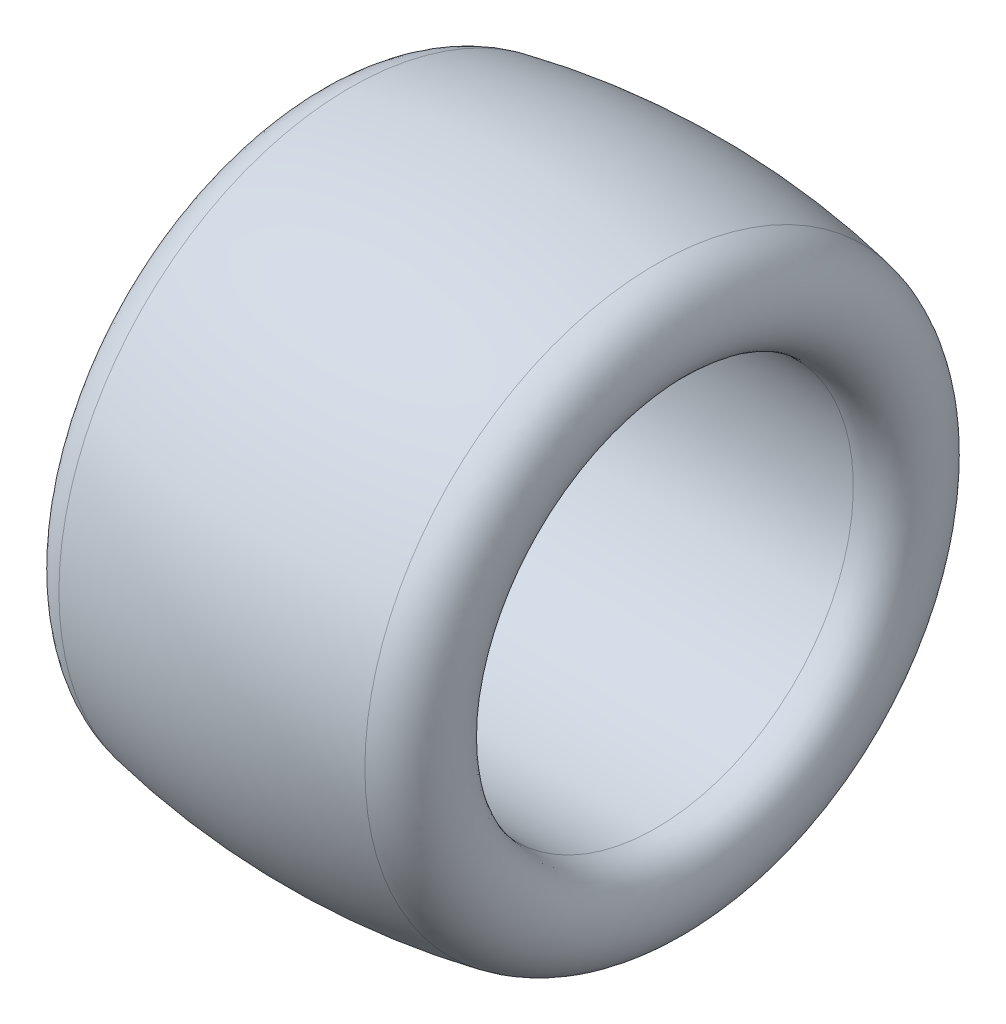
SolidWorks part; units mm, degrees
material "POLYURETHANE (11671)"
ref_plane "Front" through (0, 0, 0) normal (0, 0, 1) x (1, 0, 0)
ref_plane "Top" through (0, 0, 0) normal (0, 1, 0) x (1, 0, 0)
ref_plane "Right" through (0, 0, 0) normal (1, 0, 0) x (0, 0, -1)
sketch "Sketch1" plane through (0, 0, 0) normal (0, 0, 1) x (1, 0, 0)
  line L0 (-19.685, 0) -> (19.685, 0) construction
  line L1 (0, 0) -> (0, 39.37) construction
  line L2 (-19.685, 37.465) -> (19.685, 37.465) construction
  line L3 (-19.685, 25.4) -> (19.685, 25.4)
  arc A0 (-19.685, 37.465) -> (19.685, 37.465) centre (0, -63.2883) cw
  spline S0 degree 3 poles (19.685, 25.4) (26.8232, 25.4) (26.6187, 36.1103) (19.685, 37.465) knots 0 0 0 0 1 1 1 1
  spline S1 degree 3 poles (-19.685, 25.4) (-26.8232, 25.4) (-26.6187, 36.1103) (-19.685, 37.465) knots 0 0 0 0 1 1 1 1
  dimension "D1" = 39.37
  dimension "D2" = 78.74
  dimension "D3" = 74.93
  dimension "D4" = 50.8
revolve "Revolve1" add sketch "Sketch1" angle 360 about L0
sketch "Sketch2" plane through (0, 0, 0) normal (0, 1, 0) x (1, 0, 0)
  line L0 (6.6675, 6.9723) -> (5.9434, 4.6348)
  line L1 (-6.6675, -6.9723) -> (6.6675, -6.9723) construction
  line L2 (-6.6675, -6.9723) -> (-6.6675, 6.9723) construction
  line L3 (-6.6675, 6.9723) -> (6.6675, 6.9723) construction
  line L4 (6.6675, -6.9723) -> (6.6675, 6.9723) construction
  line L5 (-6.6675, -6.9723) -> (6.6675, 6.9723) construction
  line L6 (-6.6675, 6.9723) -> (6.6675, -6.9723) construction
  line L7 (2.8425, 1.1742) -> (6.3055, 2.9736)
  line L8 (6.3055, 2.9736) -> (5.9434, 0.5933)
  line L9 (0, -6.9723) -> (0, 6.9723) construction
  line L10 (0, 0.5933) -> (0.7762, 4.6348)
  line L11 (0.7762, 4.6348) -> (0, 5.4462)
  line L12 (-6.6675, -6.9723) -> (-6.6675, 6.9723) construction
  line L13 (-0.7762, 4.6348) -> (0, 5.4462)
  line L14 (0, 0.5933) -> (-0.7762, 4.6348)
  line L15 (-6.3055, 2.9736) -> (-5.9434, 0.5933)
  line L16 (-2.8425, 1.1742) -> (-6.3055, 2.9736)
  line L17 (-6.6675, 6.9723) -> (-5.9434, 4.6348)
  line L18 (9.4922, -3.0025) -> (11.9196, -2.5168)
  line L19 (16.337, 1.4757) -> (15.4082, -1.8188)
  line L20 (17.5191, 6.2161) -> (15.0333, 5.7187)
  line L21 (8.9501, 7.2896) -> (12.8605, 8.4894)
  line L22 (8.5629, -2.0732) -> (9.4922, -3.0025)
  line L23 (10.5041, 4.8125) -> (12.9978, 2.1181) construction
  line L24 (17.5191, 6.2161) -> (18.3738, 5.2178)
  line L25 (9.0276, -2.5378) -> (12.7069, 0.8675) construction
  line L26 (8.7818, 6.9723) -> (9.085, 5.9841)
  line L27 (10.3742, 1.2357) -> (11.5105, 1.6617)
  line L28 (11.9196, -2.5168) -> (13.7769, 5.4673)
  line L29 (0, 0) -> (0, 23.7829) construction
  line L31 (13.176, -2.2654) -> (15.0333, 5.7187)
  line L32 (11.5105, 1.6617) -> (11.7245, 1.091)
  line L33 (16.337, 1.4757) -> (15.2819, 0.9443)
  line L34 (13.7769, 5.4673) -> (11.4351, 4.9988)
  line L35 (14.2335, 2.2804) -> (17.9465, 5.717) construction
  line L36 (13.9551, 1.0838) -> (16.4489, -1.6106) construction
  line L37 (-16.4616, 1.9177) -> (-16.907, 2.2853) construction
  line L38 (13.176, -2.2654) -> (15.4082, -1.8188)
  line L39 (-10.2516, 0.8006) -> (-11.7245, 1.091) construction
  line L40 (9.1867, 0.1394) -> (11.7245, 1.091)
  line L41 (15.2819, 0.9443) -> (14.9642, 1.575)
  line L42 (17.7412, 2.9736) -> (14.9642, 1.575)
  line L43 (10.2516, 0.8006) -> (11.7245, 1.091) construction
  line L44 (9.1867, 0.1394) -> (8.5629, -2.0732)
  line L45 (10.3742, 1.2357) -> (11.4351, 4.9988)
  line L46 (-13.9551, 1.0838) -> (-16.4489, -1.6106) construction
  line L47 (16.4616, 1.9177) -> (16.907, 2.2853) construction
  line L48 (17.7412, 2.9736) -> (18.3738, 5.2178)
  line L49 (13.1778, 8.3211) -> (13.481, 7.3329)
  line L50 (-14.2335, 2.2804) -> (-17.9465, 5.717) construction
  line L51 (-9.0276, -2.5378) -> (-12.7069, 0.8675) construction
  line L52 (-10.5041, 4.8125) -> (-12.9978, 2.1181) construction
  line L53 (-17.7412, 2.9736) -> (-18.3738, 5.2178)
  line L54 (-10.3742, 1.2357) -> (-11.4351, 4.9988)
  line L55 (-9.1867, 0.1394) -> (-8.5629, -2.0732)
  line L56 (-17.7412, 2.9736) -> (-14.9642, 1.575)
  line L57 (-15.2819, 0.9443) -> (-14.9642, 1.575)
  line L58 (-9.1867, 0.1394) -> (-11.7245, 1.091)
  line L59 (-13.176, -2.2654) -> (-15.4082, -1.8188)
  line L60 (-13.7769, 5.4673) -> (-11.4351, 4.9988)
  line L61 (-16.337, 1.4757) -> (-15.2819, 0.9443)
  line L62 (-11.5105, 1.6617) -> (-11.7245, 1.091)
  line L63 (-13.176, -2.2654) -> (-15.0333, 5.7187)
  line L64 (-9.393, 0.8713) -> (-9.3984, 0.8698)
  line L65 (-11.9196, -2.5168) -> (-13.7769, 5.4673)
  line L66 (-10.3742, 1.2357) -> (-11.5105, 1.6617)
  line L67 (-9.3919, 0.8673) -> (-9.3984, 0.8698)
  line L68 (-17.5191, 6.2161) -> (-18.3738, 5.2178)
  line L69 (-8.5629, -2.0732) -> (-9.4922, -3.0025)
  line L70 (-9.393, 0.8713) -> (-9.3919, 0.8673)
  line L71 (-17.5191, 6.2161) -> (-15.0333, 5.7187)
  line L72 (-16.337, 1.4757) -> (-15.4082, -1.8188)
  line L73 (-9.4922, -3.0025) -> (-11.9196, -2.5168)
  line L74 (9.4023, 5.8158) -> (13.3127, 7.0156)
  line L75 (8.7073, 7.2151) -> (13.5555, 7.0901) construction
  line L76 (13.1033, 8.5639) -> (9.1595, 5.7413) construction
  line L77 (-13.1033, 8.5639) -> (-9.1595, 5.7413) construction
  line L78 (-8.7073, 7.2151) -> (-13.5555, 7.0901) construction
  line L79 (-9.4023, 5.8158) -> (-13.3127, 7.0156)
  line L80 (-13.1778, 8.3211) -> (-13.481, 7.3329)
  line L81 (-8.7818, 6.9723) -> (-9.085, 5.9841)
  line L82 (-8.9501, 7.2896) -> (-12.8605, 8.4894)
  arc A0 (8.7818, 6.9723) -> (8.9501, 7.2896) centre (9.0246, 7.0468) cw
  arc A1 (9.085, 5.9841) -> (9.4023, 5.8158) centre (9.3278, 6.0586) ccw
  arc A2 (13.481, 7.3329) -> (13.3127, 7.0156) centre (13.2382, 7.2584) cw
  arc A3 (12.8605, 8.4894) -> (13.1778, 8.3211) centre (12.935, 8.2466) cw
  arc A4 (-12.8605, 8.4894) -> (-13.1778, 8.3211) centre (-12.935, 8.2466) ccw
  arc A5 (-13.481, 7.3329) -> (-13.3127, 7.0156) centre (-13.2382, 7.2584) ccw
  arc A6 (-9.085, 5.9841) -> (-9.4023, 5.8158) centre (-9.3278, 6.0586) cw
  arc A7 (-8.7818, 6.9723) -> (-8.9501, 7.2896) centre (-9.0246, 7.0468) ccw
  spline S0 degree 2 poles (0, -6.9723) (2.9628, -1.1279) (5.9434, 0.5933) knots 0 0 0 1 1 1
  spline S1 degree 3 poles (0, -3.2551) (2.8645, 7.3786) (3.6765, 6.7647) (6.6675, 6.9723) knots 0 0 0 0 1 1 1 1
  spline S2 degree 2 poles (5.9434, 4.6348) (3.9953, 3.9463) (2.8425, 1.1742) knots 0 0 0 1 1 1
  spline S3 degree 2 poles (-5.9434, 4.6348) (-3.9953, 3.9463) (-2.8425, 1.1742) knots 0 0 0 1 1 1
  spline S4 degree 3 poles (0, -3.2551) (-2.8645, 7.3786) (-3.6765, 6.7647) (-6.6675, 6.9723) knots 0 0 0 0 1 1 1 1
  spline S5 degree 2 poles (0, -6.9723) (-2.9628, -1.1279) (-5.9434, 0.5933) knots 0 0 0 1 1 1
  point P0 (0, 0)
  point P32 (13.4765, 1.601)
  point P34 (9.8939, 0.7301)
  point P44 (16.5115, 1.9589)
  point P45 (11.1314, 7.1526)
  point P90 (-16.5115, 1.9589)
  point P91 (-9.8939, 0.7301)
  point P92 (-13.4765, 1.601)
  point P123 (-11.1314, 7.1526)
  dimension "D15" = 0.254
  dimension "D2" = 13.335
  dimension "D3" = 0.7762
  dimension "D4" = 2.8425
  dimension "D5" = 5.9434
  dimension "D6" = 6.3055
  dimension "D14" = 4.8529
extrude "Boss-Extrude1" [suppressed] add sketch "Sketch2" along normal offset from surface (1.5491 mm away) 1.524 from surface offset beyond the face yes
sketch "Sketch4" plane through (0, 0, 0) normal (0, 1, 0) x (1, 0, 0)
  line L0 (22.9421, -1.4091) -> (22.9421, -6.1459)
  line L1 (22.9421, -6.1459) -> (19.0342, -7.3301)
  line L2 (19.0342, -7.3301) -> (17.85, -5.5538)
  line L3 (17.85, -5.5538) -> (19.0342, -4.7644)
  line L4 (19.0342, -4.7644) -> (17.3237, -4.7644)
  line L5 (17.3237, -4.7644) -> (16.2286, -3.1217)
  line L6 (16.2286, -3.1217) -> (22.9421, -1.4091)
  line L7 (0, 1.27) -> (0, 18.5832) construction
  line L8 (-16.2286, -3.1217) -> (-22.9421, -1.4091)
  line L9 (-17.3237, -4.7644) -> (-16.2286, -3.1217)
  line L10 (-19.0342, -4.7644) -> (-17.3237, -4.7644)
  line L11 (-17.85, -5.5538) -> (-19.0342, -4.7644)
  line L12 (-19.0342, -7.3301) -> (-17.85, -5.5538)
  line L13 (-22.9421, -6.1459) -> (-19.0342, -7.3301)
  line L14 (-22.9421, -1.4091) -> (-22.9421, -6.1459)
extrude "Boss-Extrude2" [suppressed] add sketch "Sketch4" along normal blind 10.668 from offset 33.02
sketch "Sketch5" [suppressed] plane through (0, 0, 0) normal (0, 0, 1) x (1, 0, 0)
  line L0 (0, 0) -> (0, 48.6382) construction
  line L1 (-31.75, 35.9382) -> (-31.75, 48.6382)
  line L2 (-31.75, 48.6382) -> (31.75, 48.6382)
  line L3 (31.75, 48.6382) -> (31.75, 35.9382)
  arc A0 (-13.703, 39.9889) -> (-15.921, 39.6703) centre (0, -63.2883) ccw
  arc A1 (-13.703, 39.9889) -> (-15.921, 39.6703) centre (0, -63.2883) ccw construction
  arc A2 (-9.1474, 40.4916) -> (-12.5051, 40.1408) centre (0, -63.2883) ccw
  arc A3 (-9.1474, 40.4916) -> (-12.5051, 40.1408) centre (0, -63.2883) ccw construction
  arc A4 (-0.9082, 40.89) -> (-5.0678, 40.7707) centre (0, -63.2883) ccw
  arc A5 (5.0678, 40.7707) -> (0.9082, 40.89) centre (0, -63.2883) ccw
  arc A6 (5.0678, 40.7707) -> (0.9082, 40.89) centre (0, -63.2883) ccw construction
  arc A7 (-0.9082, 40.89) -> (-5.0678, 40.7707) centre (0, -63.2883) ccw construction
  arc A8 (12.5051, 40.1408) -> (9.1474, 40.4916) centre (0, -63.2883) ccw
  arc A9 (12.5051, 40.1408) -> (9.1474, 40.4916) centre (0, -63.2883) ccw construction
  arc A11 (15.6953, 39.7049) -> (13.9979, 39.9493) centre (0, -63.2883) ccw construction
  arc A12 (-31.75, 35.9382) -> (31.75, 35.9382) centre (0, -63.2883) cw
  dimension "D1" = 12.7
  dimension "D2" = 63.5
revolve "Cut-Revolve1" [suppressed] cut sketch "Sketch5" angle 360
fillet "Fillet4" [suppressed] radius 1.905 tangent propagation no
fillet "Fillet3" [suppressed] radius 0.254
pattern_circular "CirPattern4" [suppressed] count 18 over 360 of bodies 105
sketch "Sketch6" plane through (0, 0, 0) normal (1, 0, 0) x (0, 0, -1)
  circle A0 centre (0, 0) radius 28.4972 construction
  text T0 "SPORTTRAXX   TALON                       6.3 x 3.5 - 3.8                      TRAXXAS"
extrude "Boss-Extrude3" [suppressed] add sketch "Sketch6" along normal offset from surface (25.08 mm away) 0.3048 offset beyond the face yes
sketch "Sketch7" plane through (0, 0, 0) normal (1, 0, 0) x (0, 0, -1)
  circle A0 centre (0, 0) radius 29.1411 construction
  text T0 "SPORTTRAXX                      3.25 x 1.8 - 2.0                       TRAXXAS " font "Century Gothic" height 3.175
extrude "Boss-Extrude4" [suppressed] add sketch "Sketch7" against normal offset from surface (25.15 mm away) 0.254 offset beyond the face yes
scale "Scale1" scale about centroid uniform scaling yes scale factor 2
